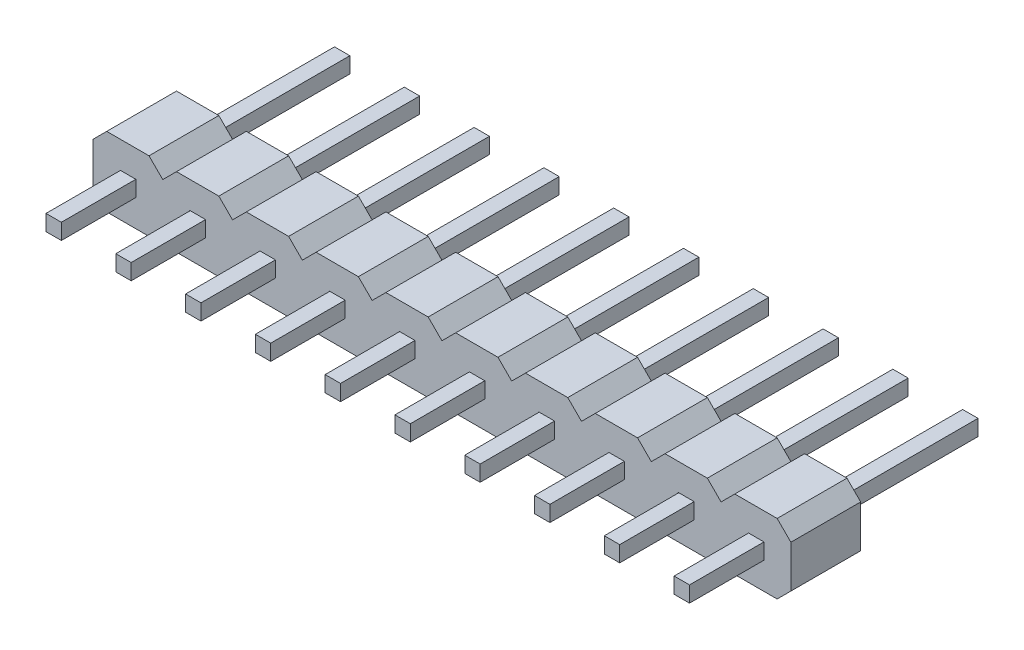
SolidWorks part; units mm, degrees
ref_plane "Front Plane" through (0, 0, 0) normal (0, 0, 1) x (1, 0, 0)
ref_plane "Top Plane" through (0, 0, 0) normal (0, 1, 0) x (1, 0, 0)
ref_plane "Right Plane" through (0, 0, 0) normal (1, 0, 0) x (0, 0, -1)
sketch "Sketch1" plane through (0, 0, 0) normal (0, 0, 1) x (1, 0, 0)
  line L0 (-37.9464, 14.2791) -> (-37.4464, 14.7791)
  line L1 (-37.4464, 14.7791) -> (-35.9064, 14.7791)
  line L2 (-37.9464, 14.2791) -> (-37.9464, 12.7391)
  line L3 (-37.4464, 12.2391) -> (-35.9064, 12.2391)
  line L4 (-12.5464, 14.2791) -> (-12.5464, 12.7391)
  line L5 (-35.9064, 14.7791) -> (-35.4064, 14.2791)
  line L6 (-37.9464, 12.7391) -> (-37.4464, 12.2391)
  line L7 (-35.9064, 12.2391) -> (-35.4064, 12.7391)
  line L8 (-34.9064, 12.2391) -> (-33.3664, 12.2391)
  line L9 (-33.3664, 12.2391) -> (-32.8664, 12.7391)
  line L10 (-35.4064, 12.7391) -> (-34.9064, 12.2391)
  line L11 (-33.3664, 14.7791) -> (-32.8664, 14.2791)
  line L12 (-34.9064, 14.7791) -> (-33.3664, 14.7791)
  line L13 (-35.4064, 14.2791) -> (-34.9064, 14.7791)
  line L14 (-32.3664, 12.2391) -> (-30.8264, 12.2391)
  line L15 (-30.8264, 12.2391) -> (-30.3264, 12.7391)
  line L16 (-32.8664, 12.7391) -> (-32.3664, 12.2391)
  line L17 (-30.8264, 14.7791) -> (-30.3264, 14.2791)
  line L18 (-32.3664, 14.7791) -> (-30.8264, 14.7791)
  line L19 (-32.8664, 14.2791) -> (-32.3664, 14.7791)
  line L20 (-29.8264, 12.2391) -> (-28.2864, 12.2391)
  line L21 (-28.2864, 12.2391) -> (-27.7864, 12.7391)
  line L22 (-30.3264, 12.7391) -> (-29.8264, 12.2391)
  line L23 (-28.2864, 14.7791) -> (-27.7864, 14.2791)
  line L24 (-29.8264, 14.7791) -> (-28.2864, 14.7791)
  line L25 (-30.3264, 14.2791) -> (-29.8264, 14.7791)
  line L26 (-27.2864, 12.2391) -> (-25.7464, 12.2391)
  line L27 (-25.7464, 12.2391) -> (-25.2464, 12.7391)
  line L28 (-27.7864, 12.7391) -> (-27.2864, 12.2391)
  line L29 (-25.7464, 14.7791) -> (-25.2464, 14.2791)
  line L30 (-27.2864, 14.7791) -> (-25.7464, 14.7791)
  line L31 (-27.7864, 14.2791) -> (-27.2864, 14.7791)
  line L32 (-24.7464, 12.2391) -> (-23.2064, 12.2391)
  line L33 (-23.2064, 12.2391) -> (-22.7064, 12.7391)
  line L34 (-25.2464, 12.7391) -> (-24.7464, 12.2391)
  line L35 (-23.2064, 14.7791) -> (-22.7064, 14.2791)
  line L36 (-24.7464, 14.7791) -> (-23.2064, 14.7791)
  line L37 (-25.2464, 14.2791) -> (-24.7464, 14.7791)
  line L38 (-22.2064, 12.2391) -> (-20.6664, 12.2391)
  line L39 (-20.6664, 12.2391) -> (-20.1664, 12.7391)
  line L40 (-22.7064, 12.7391) -> (-22.2064, 12.2391)
  line L41 (-20.6664, 14.7791) -> (-20.1664, 14.2791)
  line L42 (-22.2064, 14.7791) -> (-20.6664, 14.7791)
  line L43 (-22.7064, 14.2791) -> (-22.2064, 14.7791)
  line L44 (-19.6664, 12.2391) -> (-18.1264, 12.2391)
  line L45 (-18.1264, 12.2391) -> (-17.6264, 12.7391)
  line L46 (-20.1664, 12.7391) -> (-19.6664, 12.2391)
  line L47 (-18.1264, 14.7791) -> (-17.6264, 14.2791)
  line L48 (-19.6664, 14.7791) -> (-18.1264, 14.7791)
  line L49 (-20.1664, 14.2791) -> (-19.6664, 14.7791)
  line L50 (-17.1264, 12.2391) -> (-15.5864, 12.2391)
  line L51 (-15.5864, 12.2391) -> (-15.0864, 12.7391)
  line L52 (-17.6264, 12.7391) -> (-17.1264, 12.2391)
  line L53 (-15.5864, 14.7791) -> (-15.0864, 14.2791)
  line L54 (-17.1264, 14.7791) -> (-15.5864, 14.7791)
  line L55 (-17.6264, 14.2791) -> (-17.1264, 14.7791)
  line L56 (-14.5864, 12.2391) -> (-13.0464, 12.2391)
  line L57 (-13.0464, 12.2391) -> (-12.5464, 12.7391)
  line L58 (-15.0864, 12.7391) -> (-14.5864, 12.2391)
  line L59 (-13.0464, 14.7791) -> (-12.5464, 14.2791)
  line L60 (-14.5864, 14.7791) -> (-13.0464, 14.7791)
  line L61 (-15.0864, 14.2791) -> (-14.5864, 14.7791)
  line L62 (-16.6464, 13.7991) -> (-16.0664, 13.7991)
  line L63 (-14.1064, 13.2191) -> (-13.5264, 13.2191)
  line L64 (-14.1064, 13.2191) -> (-14.1064, 13.7991)
  line L65 (-14.1064, 13.7991) -> (-13.5264, 13.7991)
  line L66 (-13.5264, 13.2191) -> (-13.5264, 13.7991)
  line L67 (-16.0664, 13.2191) -> (-16.0664, 13.7991)
  line L68 (-16.6464, 13.2191) -> (-16.0664, 13.2191)
  line L69 (-16.6464, 13.2191) -> (-16.6464, 13.7991)
  line L70 (-19.1864, 13.7991) -> (-18.6064, 13.7991)
  line L71 (-18.6064, 13.2191) -> (-18.6064, 13.7991)
  line L72 (-19.1864, 13.2191) -> (-18.6064, 13.2191)
  line L73 (-19.1864, 13.2191) -> (-19.1864, 13.7991)
  line L74 (-21.7264, 13.7991) -> (-21.1464, 13.7991)
  line L75 (-21.1464, 13.2191) -> (-21.1464, 13.7991)
  line L76 (-21.7264, 13.2191) -> (-21.1464, 13.2191)
  line L77 (-21.7264, 13.2191) -> (-21.7264, 13.7991)
  line L78 (-24.2664, 13.7991) -> (-23.6864, 13.7991)
  line L79 (-23.6864, 13.2191) -> (-23.6864, 13.7991)
  line L80 (-24.2664, 13.2191) -> (-23.6864, 13.2191)
  line L81 (-24.2664, 13.2191) -> (-24.2664, 13.7991)
  line L82 (-26.8064, 13.7991) -> (-26.2264, 13.7991)
  line L83 (-26.2264, 13.2191) -> (-26.2264, 13.7991)
  line L84 (-26.8064, 13.2191) -> (-26.2264, 13.2191)
  line L85 (-26.8064, 13.2191) -> (-26.8064, 13.7991)
  line L86 (-29.3464, 13.7991) -> (-28.7664, 13.7991)
  line L87 (-28.7664, 13.2191) -> (-28.7664, 13.7991)
  line L88 (-29.3464, 13.2191) -> (-28.7664, 13.2191)
  line L89 (-29.3464, 13.2191) -> (-29.3464, 13.7991)
  line L90 (-31.8864, 13.7991) -> (-31.3064, 13.7991)
  line L91 (-31.3064, 13.2191) -> (-31.3064, 13.7991)
  line L92 (-31.8864, 13.2191) -> (-31.3064, 13.2191)
  line L93 (-31.8864, 13.2191) -> (-31.8864, 13.7991)
  line L94 (-34.4264, 13.7991) -> (-33.8464, 13.7991)
  line L95 (-33.8464, 13.2191) -> (-33.8464, 13.7991)
  line L96 (-34.4264, 13.2191) -> (-33.8464, 13.2191)
  line L97 (-34.4264, 13.2191) -> (-34.4264, 13.7991)
  line L98 (-36.9664, 13.7991) -> (-36.3864, 13.7991)
  line L99 (-36.3864, 13.2191) -> (-36.3864, 13.7991)
  line L100 (-36.9664, 13.2191) -> (-36.3864, 13.2191)
  line L101 (-36.9664, 13.2191) -> (-36.9664, 13.7991)
  point P0 (-37.9464, 14.7791)
  point P1 (-35.4064, 12.2391)
  point P2 (-37.9464, 12.2391)
  point P3 (-35.4064, 14.7791)
  dimension "D1" = 2.54
  dimension "D3" = 0.58
  dimension "D4" = 0.58
  dimension "D5" = 0.98
  dimension "D6" = 0.98
  dimension "D2" = 10
  dimension "D7" = 10
extrude "Boss-Extrude1" add sketch "Sketch1" along normal blind 2.54
sketch "Sketch2" plane through (0, 0, 0) normal (0, 0, 1) x (1, 0, 0)
  line L0 (-16.6255, 13.2232) -> (-16.6255, 13.7991)
  line L1 (-14.0855, 13.2232) -> (-13.5264, 13.2232)
  line L2 (-14.0855, 13.2232) -> (-14.0855, 13.7991)
  line L3 (-14.0855, 13.7991) -> (-13.5264, 13.7991)
  line L4 (-13.5264, 13.2232) -> (-13.5264, 13.7991)
  line L5 (-16.6255, 13.2232) -> (-16.0664, 13.2232)
  line L6 (-16.6255, 13.7991) -> (-16.0664, 13.7991)
  line L7 (-16.0664, 13.2232) -> (-16.0664, 13.7991)
  line L8 (-19.1655, 13.2232) -> (-19.1655, 13.7991)
  line L9 (-19.1655, 13.2232) -> (-18.6064, 13.2232)
  line L10 (-19.1655, 13.7991) -> (-18.6064, 13.7991)
  line L11 (-18.6064, 13.2232) -> (-18.6064, 13.7991)
  line L12 (-21.7055, 13.2232) -> (-21.7055, 13.7991)
  line L13 (-21.7055, 13.2232) -> (-21.1464, 13.2232)
  line L14 (-21.7055, 13.7991) -> (-21.1464, 13.7991)
  line L15 (-21.1464, 13.2232) -> (-21.1464, 13.7991)
  line L16 (-24.2455, 13.2232) -> (-24.2455, 13.7991)
  line L17 (-24.2455, 13.2232) -> (-23.6864, 13.2232)
  line L18 (-24.2455, 13.7991) -> (-23.6864, 13.7991)
  line L19 (-23.6864, 13.2232) -> (-23.6864, 13.7991)
  line L20 (-26.7855, 13.2232) -> (-26.7855, 13.7991)
  line L21 (-26.7855, 13.2232) -> (-26.2264, 13.2232)
  line L22 (-26.7855, 13.7991) -> (-26.2264, 13.7991)
  line L23 (-26.2264, 13.2232) -> (-26.2264, 13.7991)
  line L24 (-29.3255, 13.2232) -> (-29.3255, 13.7991)
  line L25 (-29.3255, 13.2232) -> (-28.7664, 13.2232)
  line L26 (-29.3255, 13.7991) -> (-28.7664, 13.7991)
  line L27 (-28.7664, 13.2232) -> (-28.7664, 13.7991)
  line L28 (-31.8655, 13.2232) -> (-31.8655, 13.7991)
  line L29 (-31.8655, 13.2232) -> (-31.3064, 13.2232)
  line L30 (-31.8655, 13.7991) -> (-31.3064, 13.7991)
  line L31 (-31.3064, 13.2232) -> (-31.3064, 13.7991)
  line L32 (-34.4055, 13.2232) -> (-34.4055, 13.7991)
  line L33 (-34.4055, 13.2232) -> (-33.8464, 13.2232)
  line L34 (-34.4055, 13.7991) -> (-33.8464, 13.7991)
  line L35 (-33.8464, 13.2232) -> (-33.8464, 13.7991)
  line L36 (-36.9455, 13.2232) -> (-36.9455, 13.7991)
  line L37 (-36.9455, 13.2232) -> (-36.3864, 13.2232)
  line L38 (-36.9455, 13.7991) -> (-36.3864, 13.7991)
  line L39 (-36.3864, 13.2232) -> (-36.3864, 13.7991)
  dimension "D1" = 10
extrude "Boss-Extrude2" add sketch "Sketch2" along normal blind 5.25 and the other way blind 5.25
